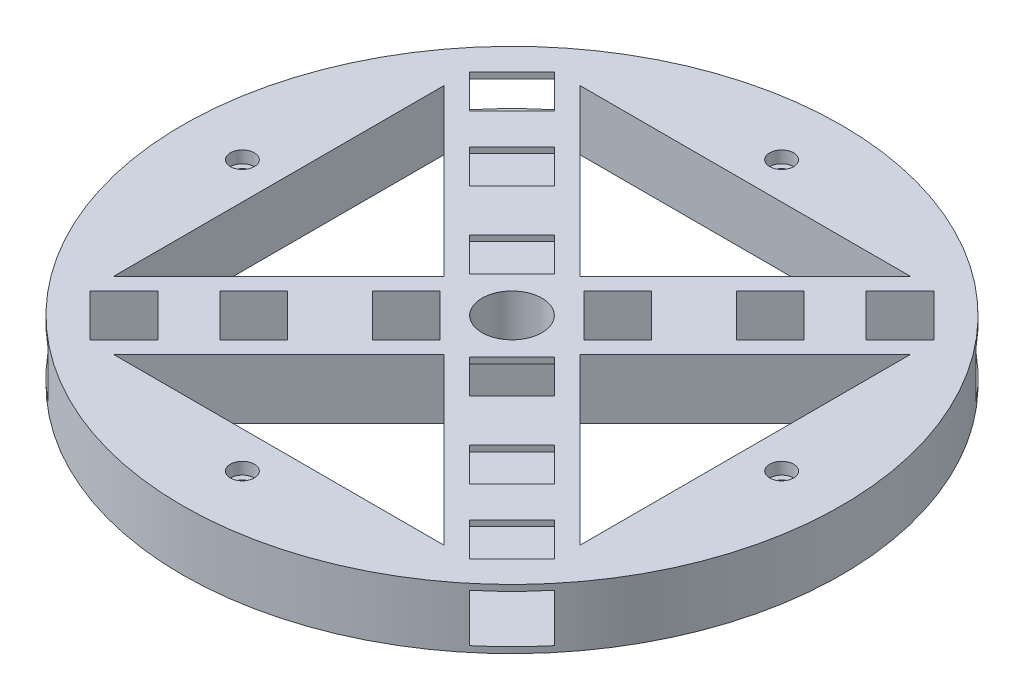
SolidWorks part; units mm, degrees
ref_plane "前视基准面" through (0, 0, 0) normal (0, 0, 1) x (1, 0, 0)
ref_plane "上视基准面" through (0, 0, 0) normal (0, 1, 0) x (1, 0, 0)
ref_plane "右视基准面" through (0, 0, 0) normal (1, 0, 0) x (0, 0, -1)
sketch "草图2" plane through (0, 0, 0) normal (0, 1, 0) x (1, 0, 0)
  line L2 (-13.7886, 19.4454) -> (13.7886, 19.4454)
  line L3 (-19.4454, 13.7886) -> (-19.4454, -13.7886)
  line L4 (-13.7886, -19.4454) -> (13.7886, -19.4454)
  line L5 (19.4454, 13.7886) -> (19.4454, -13.7886)
  line L6 (-19.4454, 19.4454) -> (-2.8284, 2.8284) construction
  line L7 (-19.4454, -19.4454) -> (-2.8284, -2.8284) construction
  line L8 (5.6569, 0) -> (19.4454, -13.7886)
  line L10 (13.7886, -19.4454) -> (0, -5.6569)
  line L12 (0, -5.6569) -> (-13.7886, -19.4454)
  line L14 (-19.4454, -13.7886) -> (-5.6569, 0)
  line L16 (-5.6569, 0) -> (-19.4454, 13.7886)
  line L18 (-13.7886, 19.4454) -> (0, 5.6569)
  line L20 (0, 5.6569) -> (13.7886, 19.4454)
  line L22 (19.4454, 13.7886) -> (5.6569, 0)
  line L30 (2.8284, 2.8284) -> (19.4454, 19.4454) construction
  circle A0 centre (0, 0) radius 27.5
  circle A2 centre (0, 22.5) radius 0.525
  circle A3 centre (22.5, 0) radius 0.525
  circle A4 centre (0, -22.5) radius 0.525
  circle A5 centre (-22.5, 0) radius 0.525
  point P15 (0, 0)
  point P20 (0, 0)
  point P37 (0, 0)
  dimension "D1" = 55
  dimension "D2" = 4
  dimension "D4" = 1.05
  dimension "D3" = 4
extrude "凸台-拉伸1" add sketch "草图2" along normal blind 5
ref_plane "基准面4" through (2.8284, 0, -2.8284) normal (-0.7071, 0, 0.7071) x (0.7071, 0, 0.7071)
sketch "草图5" plane through (2.8284, 0, -2.8284) normal (-0.7071, 0, 0.7071) x (0.7071, 0, 0.7071)
  line L0 (0, 0) -> (0, 5)
  line L1 (27.5, 5) -> (-27.5, 5) construction
  line L3 (-2.5, 4.5) -> (2.5, 4.5)
  line L4 (-2.5, 4.5) -> (-2.5, 0.5)
  line L5 (-2.5, 0.5) -> (2.5, 0.5)
  line L6 (2.5, 4.5) -> (2.5, 0.5)
  line L7 (-2.5, 4.5) -> (2.5, 0.5) construction
  line L8 (-2.5, 0.5) -> (2.5, 4.5) construction
  point P5 (0, 2.5)
extrude "切除-拉伸1" cut sketch "草图5" against normal through all contours L6 L5 L4 L3
ref_axis "基准轴1" through (0, 5, 0) along (0, -1, 0)
pattern_circular "阵列(圆周)1" count 4 over 360 about axis through (0, 5, 0) along (0, -1, 0) of "切除-拉伸1"
sketch "草图6" plane through (0, 5, 0) normal (0, 1, 0) x (1, 0, 0)
  line L10 (-1.2267, 4.7622) -> (-4.0551, 7.5906)
  line L13 (-4.7622, 1.2267) -> (-7.5906, 4.0551)
  line L14 (-4.7622, 1.2267) -> (-7.5906, 4.0551)
  line L15 (-7.5906, 4.0551) -> (-4.0551, 7.5906)
  line L16 (-4.0551, 7.5906) -> (-1.2267, 4.7622)
  line L17 (-1.2267, 4.7622) -> (-4.7622, 1.2267)
  line L18 (-16.5365, 13.001) -> (-19.3649, 15.8294)
  line L19 (-11.1262, 7.5906) -> (-7.5906, 11.1262)
  line L20 (-19.3649, 19.3649) -> (-19.4454, 19.4454)
  line L21 (-13.001, 16.5365) -> (-15.8294, 19.3649)
  line L22 (-11.1262, 7.5906) -> (-13.9546, 10.4191)
  line L24 (-16.5365, 13.001) -> (-19.3649, 15.8294)
  line L25 (-19.3649, 15.8294) -> (-15.8294, 19.3649)
  line L26 (-15.8294, 19.3649) -> (-13.001, 16.5365)
  line L27 (-13.001, 16.5365) -> (-16.5365, 13.001)
  line L28 (-13.9546, 10.4191) -> (-10.4191, 13.9546)
  line L30 (-10.4191, 13.9546) -> (-7.5906, 11.1262)
  line L31 (-11.1262, 7.5906) -> (-13.9546, 10.4191)
  line L32 (-7.5906, 11.1262) -> (-10.4191, 13.9546)
  circle A0 centre (0, 0) radius 27.5 construction
extrude "切除-拉伸2" cut sketch "草图6" against normal blind 2 contours L17 L10 L15 L13 | L30 L28 L22 L19 | L27 L21 L25 L18 region at (-4.4087, 5, -4.4087) region at (-16.1829, 5, -16.1829) region at (-10.7726, 5, -10.7726)
pattern_circular "阵列(圆周)2" count 4 every 90 about axis through (0, 5, 0) along (0, -1, 0) of "切除-拉伸2"
sketch "草图7" plane through (0, 5, 0) normal (0, 1, 0) x (1, 0, 0)
  circle A0 centre (0, 0) radius 2.5
extrude "切除-拉伸3" cut sketch "草图7" against normal through all
sketch "草图8" plane through (0, 5, 0) normal (0, 1, 0) x (1, 0, 0)
  circle A0 centre (-22.5, 0) radius 1
  dimension "D1" = 2
extrude "切除-拉伸4" cut sketch "草图8" against normal blind 1
pattern_circular "阵列(圆周)3" count 4 over 360 about axis through (0, 5, 0) along (0, -1, 0) of "切除-拉伸4"
